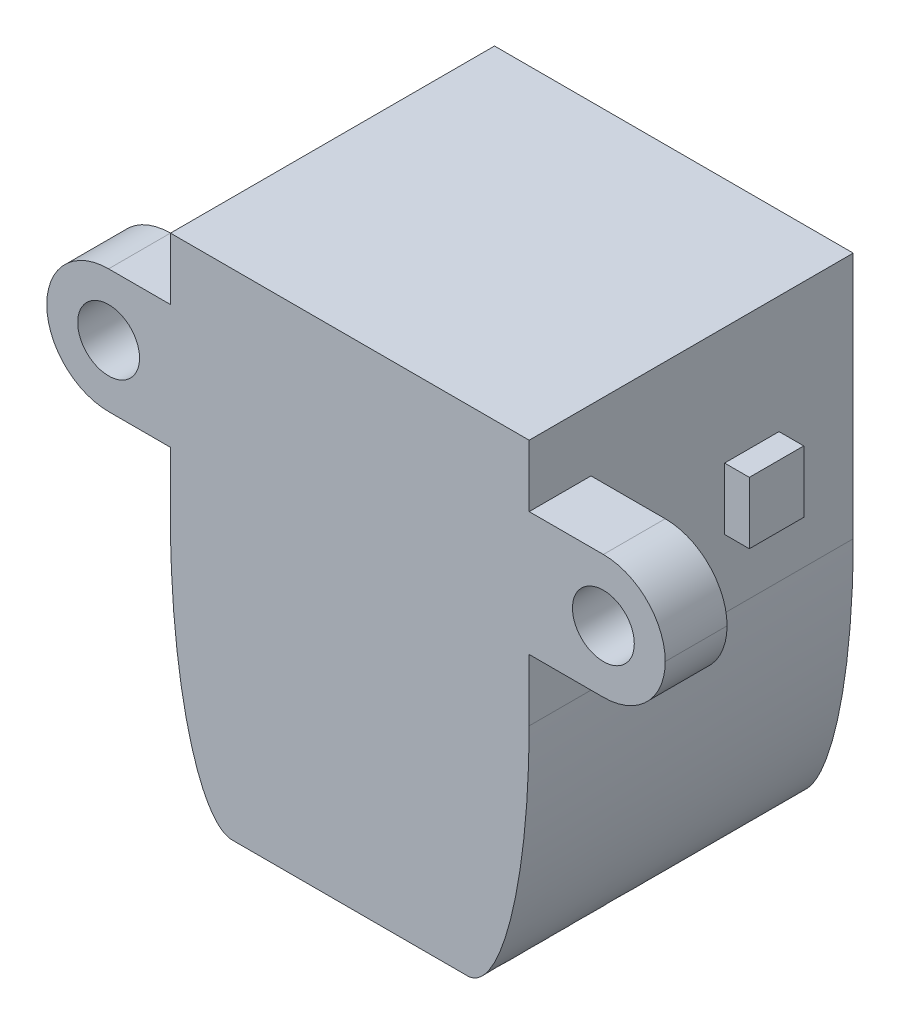
SolidWorks part; units mm, degrees
ref_plane "Front Plane" through (0, 0, 0) normal (0, 0, 1) x (1, 0, 0)
ref_plane "Top Plane" through (0, 0, 0) normal (0, 1, 0) x (1, 0, 0)
ref_plane "Right Plane" through (0, 0, 0) normal (1, 0, 0) x (0, 0, -1)
sketch "Sketch1" plane through (0, 0, 0) normal (0, 0, 1) x (1, 0, 0)
  line L1 (0, 0) -> (29, 0)
  line L2 (0, 0) -> (0, -40)
  line L3 (0, -40) -> (29, -40)
  line L4 (29, 0) -> (29, -40)
  dimension "D1" = 29
  dimension "D2" = 40
extrude "Boss-Extrude1" add sketch "Sketch1" along normal blind 26.2
sketch "Sketch3" plane through (0, 0, 26.2) normal (0, 0, 1) x (1, 0, 0)
  line L0 (14.5, 0) -> (14.5, -10) construction
  line L1 (29, 0) -> (0, 0) construction
  line L2 (0, -15) -> (29, -15) construction
  line L3 (29, -40) -> (29, 0) construction
  line L4 (0, 0) -> (0, -40) construction
  line L7 (0, -35) -> (29, -35) construction
  line L8 (0, -40) -> (29, -40) construction
  line L9 (0, -35) -> (5, -40)
  line L10 (29, -35) -> (24, -40)
  dimension "D2" = 15
  dimension "D1" = 10
  dimension "D4" = 5
  dimension "D5" = 5
  dimension "D6" = 5
fillet "Fillet1" radius 5 2 edges at (29, -40, 13.1) (0, -40, 13.1) second distance 20 first distance on face at (14.5, -40, 13.1)
sketch "Sketch5" plane through (0, 0, 0) normal (-1, 0, 0) x (0, 0, 1)
  line L0 (26.2, 0) -> (26.2, -20) construction
  line L1 (26.2, -5) -> (21.2, -5)
  line L2 (26.2, -5) -> (26.2, -15)
  line L3 (26.2, -15) -> (21.2, -15)
  line L4 (21.2, -5) -> (21.2, -15)
  line L5 (26.2, 0) -> (0, 0) construction
  dimension "D1" = 5
  dimension "D2" = 10
  dimension "D3" = 5
extrude "Boss-Extrude2" add sketch "Sketch5" along normal blind 10 and the other way blind 40
fillet "Fillet2" radius 5 4 edges at (40, -15, 23.7) (40, -5, 23.7) (-10, -15, 23.7) (-10, -5, 23.7)
sketch "Sketch6" plane through (0, 0, 26.2) normal (0, 0, 1) x (1, 0, 0)
  circle A0 centre (-5, -10) radius 2.5
  circle A1 centre (35, -10) radius 2.5
  arc A2 (-5, -5) -> (-10, -10) centre (-5, -10) ccw construction
  arc A3 (40, -10) -> (35, -5) centre (35, -10) ccw construction
  dimension "D1" = 5
  dimension "D2" = 5
extrude "Cut-Extrude2" cut sketch "Sketch6" against normal blind 6
sketch "Sketch7" plane through (29, 0, 0) normal (1, 0, 0) x (0, 0, -1)
  line L0 (-21.2, -12) -> (-8.2, -12) construction
  line L1 (-8.2, -9.5) -> (-6, -9.5)
  line L2 (-21.2, -10) -> (-21.2, -12) construction
  line L3 (-8.2, -12) -> (-8.2, -20) construction
  line L4 (-6, -9.5) -> (-6, -12)
  line L5 (-26.2, -20) -> (0, -20) construction
  line L6 (-6, -12) -> (-6, -14.5)
  line L7 (-6, -14.5) -> (-8.2, -14.5)
  line L8 (-10.4, -12) -> (-10.4, -14.5)
  line L9 (-10.4, -14.5) -> (-8.2, -14.5)
  line L10 (-8.2, -9.5) -> (-10.4, -9.5)
  line L11 (-10.4, -9.5) -> (-10.4, -12)
  dimension "D1" = 2.2
  dimension "D2" = 13
  dimension "D3" = 2
  dimension "D4" = 5
  dimension "D5" = 2.2
  dimension "D6" = 2.5
extrude "Boss-Extrude3" add sketch "Sketch7" along normal blind 2 and the other way blind 31
